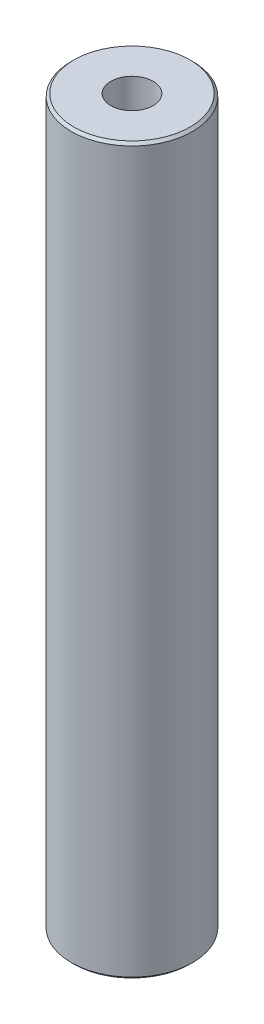
SolidWorks part; units mm, degrees
ref_plane "Front Plane" through (0, 0, 0) normal (0, 0, 1) x (1, 0, 0)
ref_plane "Top Plane" through (0, 0, 0) normal (0, 1, 0) x (1, 0, 0)
ref_plane "Right Plane" through (0, 0, 0) normal (1, 0, 0) x (0, 0, -1)
sketch "Sketch1" plane through (0, 0, 0) normal (0, 1, 0) x (1, 0, 0)
  circle A0 centre (0, 0) radius 50
  dimension "SHAFT_OD" = 100
extrude "Boss-Extrude1" add sketch "Sketch1" along normal blind 596.948
sketch "Sketch2" plane through (0, 0, 0) normal (0, 1, 0) x (1, 0, 0)
  circle A0 centre (0, 0) radius 17.3984
  dimension "BORE_D" = 34.7967
extrude "Cut-Extrude1" cut sketch "Sketch2" along normal through all
chamfer "Chamfer1" distance 2.1208 angle 45 2 edges at (0, 596.948, 50) (0, 0, 50)
